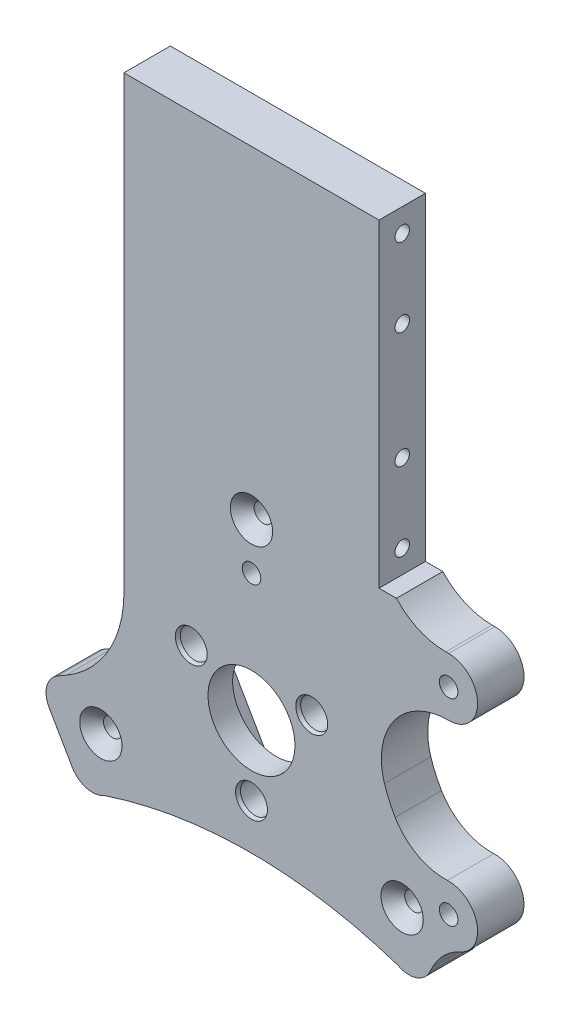
SolidWorks part; units mm, degrees
ref_plane "Front Plane" through (0, 0, 0) normal (0, 0, 1) x (1, 0, 0)
ref_plane "Top Plane" through (0, 0, 0) normal (0, 1, 0) x (1, 0, 0)
ref_plane "Right Plane" through (0, 0, 0) normal (1, 0, 0) x (0, 0, -1)
sketch "Sketch1" plane through (0, 0, 0) normal (0, 0, 1) x (1, 0, 0)
  line L0 (-1000, 0) -> (49000, 0) construction
  line L1 (0, -1000) -> (0, 49000) construction
  line L2 (0, 0) -> (-37.6779, -21.7533) construction
  line L3 (0, 0) -> (34.4865, -19.9108) construction
  line L4 (10, -8.7457) -> (10, 8.7457) construction
  line L5 (10.3863, 10.4956) -> (-10.3863, 10.4956)
  line L6 (-14.2847, 3.7444) -> (-3.9035, -14.2421)
  line L7 (3.9036, -14.242) -> (14.2846, 3.7447)
  line L8 (9.0941, -5.2486) -> (-10.3863, 5.9944) construction
  line L9 (0, -11.9891) -> (0, 10.4956) construction
  line L10 (10.3863, 5.9946) -> (-9.0941, -5.2488) construction
  line L11 (-30.909, -22.4641) -> (-34.909, -15.5359)
  line L12 (-32, -9.2376) -> (-33.4449, -10.0718)
  line L13 (-25, -23.6714) -> (-25.4449, -23.9282)
  line L14 (24.7944, -23.6821) -> (25.2453, -23.9282)
  line L15 (30.7512, -22.1827) -> (34.3345, -14.8973)
  line L16 (22, 49.7573) -> (-22, 49.7573)
  line L17 (22, 49.7573) -> (22, 38.5054)
  line L18 (32, -9.2376) -> (32.7451, -9.6678)
  line L19 (-22, 49.7573) -> (-22, 8.0829)
  line L20 (-4, 6.9282) -> (-41.6779, -14.8251) construction
  line L21 (34, 27.0109) -> (33.4945, 27.0109)
  line L22 (34, 17.0109) -> (33.8909, 17.0109)
  line L25 (-12, 0) -> (-12.0927, -0.0535)
  circle A0 centre (0, 0) radius 30 construction
  circle A1 centre (0, 0) radius 7.5
  circle A2 centre (0, 30) radius 4 construction
  circle A3 centre (25.9808, -15) radius 4 construction
  circle A4 centre (-25.9808, -15) radius 4 construction
  arc A5 (-10.3863, 10.4956) -> (-14.2847, 3.7444) centre (-10.3863, 5.9944) ccw
  arc A6 (-3.9035, -14.2421) -> (3.9036, -14.242) centre (0, -11.9891) ccw
  arc A7 (14.2846, 3.7447) -> (10.3863, 10.4956) centre (10.3863, 5.9946) ccw
  circle A8 centre (27.3746, 42.204) radius 2.5
  circle A9 centre (-27.6254, 42.204) radius 2.5
  arc A10 (32, -9.2376) -> (22.9322, 2.0481) centre (42, 8.0829) cw
  arc A11 (-22, 8.0829) -> (-32, -9.2376) centre (-42, 8.0829) cw
  arc A12 (25.2453, -23.9282) -> (-25.4449, -23.9282) centre (-0.0998, -99.8072) ccw
  arc A13 (30.7512, -22.1827) -> (25.2453, -23.9282) centre (27.1619, -20.4173) cw
  arc A14 (32.7451, -9.6678) -> (34.3345, -14.8973) centre (30.7451, -13.1319) cw
  arc A15 (-30.909, -22.4641) -> (-25.4449, -23.9282) centre (-27.4449, -20.4641) ccw
  arc A16 (-33.4449, -10.0718) -> (-34.909, -15.5359) centre (-31.4449, -13.5359) ccw
  circle A17 centre (34, -11.9891) radius 5
  arc A18 (34, 17.0109) -> (34, 27.0109) centre (34, 22.0109) ccw
  arc A19 (22, 38.5054) -> (33.4945, 27.0109) centre (33.4945, 38.5054) ccw
  arc A20 (33.8909, 17.0109) -> (22.9322, 2.0481) centre (33.8909, 5.5165) ccw
  point P4 (0, 0)
  point P19 (0, 0)
  point P21 (10, 0)
  point P40 (0, 0.9917)
  point P46 (0, 49.7573)
  point P47 (-32.909, -19)
  point P62 (28.909, -25.9282)
  point P67 (-28.909, -25.9282)
  line B0 (37, -11.9891) -> (-75, -11.9891) construction
  line B1 (0, -11.9891) -> (0, 22.0109) construction
  line B2 (-14.25, -36.1891) -> (-14.25, -11.9891) construction
  line B3 (-29.75, -13.311) -> (-29.75, -10.6672) construction
  line B4 (-39.75, -13.2558) -> (-39.75, -10.7223) construction
  line B5 (34, -11.9891) -> (34, 22.0109) construction
  line B6 (37, 27.0109) -> (37, -16.9891) construction
  line B7 (37, 27.0109) -> (-3, 27.0109) construction
  line B8 (37, -16.9891) -> (-3, -16.9891) construction
  line B9 (-14.25, -11.9891) -> (-14.25, 75.8256) construction
  line B10 (-3, 27.0109) -> (-3, -16.9891) construction
  dimension "D1" = 60
  dimension "D4" = 15
  dimension "D5" = 3
  dimension "D7" = 55
  dimension "D9" = 8
  dimension "D11" = 20
  dimension "D12" = 11.4945
  dimension "D13" = 4
  dimension "D14" = 4
  dimension "D15" = 11.4945
  dimension "D2" = 120
  dimension "D3" = 120
  dimension "D6" = 10
  dimension "D8" = 44
  dimension "D10" = 8
sketch_block_instance "HemeraFrontContraints-3"
sketch_block "HemeraFrontContraints" parameters "D1"=34, "D2"=48.25, "D3"=63.75, "D4"=73.75, "D5"=24.2, "D6"=34, "D7"=34, "D8"=31.699, "D9"=36.9763, "D10"=44
sketch "Sketch2" plane through (0, 0, 0) normal (0, 1, 0) x (1, 0, 0)
  line L0 (52, -10) -> (52, -104) construction
  line L1 (-49, 0) -> (49, 0) construction
  line L2 (-52, -10) -> (-52, -104) construction
  line L3 (-52, -104) -> (52, -104) construction
  line L4 (0, 0) -> (0, -30) construction
  line L7 (-52, -10) -> (-49, -10) construction
  line L8 (-49, 0) -> (-49, -10) construction
  line L11 (52, -10) -> (49, -10) construction
  line L12 (49, 0) -> (49, -10) construction
  point P12 (0, -104)
  dimension "D1" = 98
  dimension "D2" = 104
  dimension "D3" = 30
  dimension "D4" = 10
  dimension "D7" = 104
extrude "Boss-Extrude1" add sketch "Sketch1" along normal blind 8 contours A7 L7 A6 L6 A5 L5 | L17 | L19 | L16 L19 L17 | A10 A17 L15 A14 L18 | L15 A17 A10 L18 A14 region at (1.5486, 13.9173, 0) region at (31.8342, -12.7141, 0) region at (35.6729, -11.4291, 0)
extrude "Boss-Extrude2" add sketch "Sketch1<3>" along normal blind 4.25 from offset 3.75 contours L7 A7 L5 A5 L6 A6 A1 region at (13.936, 8.0445, 0)
sketch "Sketch1<3>" plane through (0, 0, 0) normal (0, 0, 1) x (1, 0, 0) same geometry as "Sketch1"
sketch "Sketch15" plane through (0, 49.7573, 0) normal (0, 1, 0) x (1, 0, 0)
  line L4 (22, 0) -> (-22, 0)
  line L5 (-22, 0) -> (-22, -8)
  line L6 (-22, -8) -> (22, -8)
  line L7 (22, -8) -> (22, 0)
  line L8 (22, 0) -> (-22, 0)
  line L9 (-22, 0) -> (-22, -8)
  line L10 (-22, -8) -> (22, -8)
  line L11 (22, -8) -> (22, 0)
  dimension "D1" = 0
extrude "Boss-Extrude3" add sketch "Sketch15" along normal blind 36
sketch "Sketch4" plane through (0, 0, 0) normal (0, 0, -1) x (-1, 0, 0)
  line L0 (0, 26) -> (0, 34)
  arc A0 (0, 26) -> (0, 34) centre (0, 30) ccw
revolve "Cut-Revolve1" cut sketch "Sketch4" angle 360 about L0
sketch "Sketch22" plane through (0, 0, 8) normal (0, 0, 1) x (1, 0, 0)
  line L0 (22, 49.7573) -> (22, 38.5054) construction
  line L1 (22, 40.7573) -> (27, 40.7573)
  line L2 (22, 40.7573) -> (22, 30.7573)
  line L3 (22, 30.7573) -> (27, 30.7573)
  line L4 (27, 40.7573) -> (27, 30.7573)
  dimension "D1" = 10
  dimension "D2" = 5
  dimension "D3" = 30.7573
extrude "Cut-Extrude1" cut sketch "Sketch22" against normal blind 10
sketch "Sketch5" plane through (0, 0, 0) normal (0, 0, -1) x (-1, 0, 0)
  line L0 (-22.5167, -13) -> (-29.4449, -17)
  line L1 (0, 0) -> (-34.4865, -19.9108) construction
  arc A0 (-22.5167, -13) -> (-29.4449, -17) centre (-25.9808, -15) ccw
revolve "Cut-Revolve2" cut sketch "Sketch5" angle 360 about L0
sketch "Sketch6" plane through (0, 0, 0) normal (0, 0, -1) x (-1, 0, 0)
  line L0 (22.5167, -13) -> (29.4449, -17)
  line L1 (0, 0) -> (37.6779, -21.7533) construction
  arc A0 (22.5167, -13) -> (29.4449, -17) centre (25.9808, -15) ccw
revolve "Cut-Revolve3" cut sketch "Sketch6" angle 360 about L0
hole_wizard "CSK for M3 Flat Head Machine Screw1" positions "Sketch7" profile "Sketch8" countersink size "M3" standard "ANSI Metric" end condition through all
sketch "Sketch7" plane through (0, 0, 8) normal (0, 0, 1) x (1, 0, 0)
  point P0 (0, 30)
  point P3 (25.9808, -15)
  point P6 (-25.9808, -15)
sketch "Sketch8" plane through (0, 30, 8) normal (1, 0, 0) x (0, -1, 0)
  line L0 (0, 0) -> (0, 8)
  line L1 (0, 8) -> (1.6, 8)
  line L2 (1.6, 8) -> (1.6, 2.05)
  line L3 (1.6, 2.05) -> (3.65, 0)
  line L5 (3.65, 0) -> (0, 0)
  line L6 (-1.6, 2.05) -> (-3.65, 0) construction
  line L11 (0, -6.35) -> (0, 107.95) construction
  dimension "Thru Hole Dia." = 3.2
  dimension "Thru Hole Depth" = 8
  dimension "Near C'Sink Dia." = 7.3
  dimension "Near C'Sink Angle" = 90
hole_wizard "CBORE for M3 SBHCS2" positions "Sketch11" profile "Sketch12" counterbore size "M3" standard "ANSI Metric" end condition through all
sketch "Sketch11" plane through (0, 0, 0) normal (0, 0, -1) x (-1, 0, 0)
  point P0 (-34, 22.0109)
  point P3 (0, 22.0109)
  point P6 (0, -11.9891)
  point P19 (-34, -11.9891)
sketch "Sketch12" plane through (34, 22.0109, 0) normal (1, 0, 0) x (0, 1, 0)
  line L0 (0, 0) -> (0, 8)
  line L1 (0, 8) -> (1.6, 8)
  line L3 (1.6, 8) -> (1.6, 3)
  line L4 (3.35, 3) -> (1.6, 3)
  line L5 (3.35, 3) -> (3.35, 0.025)
  line L6 (3.35, 0.025) -> (3.375, 0)
  line L7 (3.375, 0) -> (0, 0)
  line L8 (-3.35, 0.025) -> (-3.375, 0) construction
  line L11 (0, -6.35) -> (0, 107.95) construction
  dimension "Thru Hole Dia." = 3.2
  dimension "Thru Hole Depth" = 8
  dimension "C'Bore Dia." = 6.7
  dimension "C'Bore Depth" = 3
  dimension "Near C'Sink Dia." = 6.75
  dimension "Near C'Sink Angle" = 90
hole_wizard "CSK for M4 Flat Head Machine Screw1" positions "Sketch13" profile "Sketch14" countersink size "M4" standard "ANSI Metric" end condition through all
sketch "Sketch13" plane through (0, 0, 8) normal (0, 0, 1) x (1, 0, 0)
  point P0 (-10.3863, 5.9944)
  point P3 (10.3863, 5.9946)
  point P6 (0, -11.9891)
sketch "Sketch14" plane through (-10.3863, 5.9944, 8) normal (1, 0, 0) x (0, -1, 0)
  line L0 (0, 0) -> (0, 8)
  line L1 (0, 8) -> (2.5, 8)
  line L2 (2.5, 8) -> (2.5, 0.6036)
  line L3 (2.5, 0.6036) -> (2.75, 0)
  line L5 (2.75, 0) -> (0, 0)
  line L6 (-2.5, 0.6036) -> (-2.75, 0) construction
  line L11 (0, -6.35) -> (0, 107.95) construction
  dimension "Thru Hole Dia." = 5
  dimension "Thru Hole Depth" = 8
  dimension "Near C'Sink Dia." = 5.5
  dimension "Near C'Sink Angle" = 45
fillet "Fillet1" radius 10 2 edges at (30.5834, -8.3385, 4) (33.328, -16.9437, 4)
hole_wizard "Tap Drill for M3x0.5 Tap4" positions "Sketch25" profile "Sketch26" hole size "M3x0.5" standard "ANSI Metric"
sketch "Sketch25" plane through (22, 0, 0) normal (1, 0, 0) x (0, 0, -1)
  line L0 (-8, 85.7573) -> (0, 85.7573) construction
  line L1 (0, 85.7573) -> (0, 30.7573) construction
  point P0 (-4, 81.7573)
  point P2 (-4, 68.2573)
  point P4 (-4, 34.7573)
  point P6 (-4, 48.2573)
  dimension "D1" = 4
  dimension "D2" = 13.5
  dimension "D3" = 13.5
  dimension "D4" = 20
  dimension "D5" = 4
sketch "Sketch26" plane through (22, 81.7573, 4) normal (0, 1, 0) x (0, 0, -1)
  line L0 (0, 0) -> (0, 5.7511)
  line L1 (0, 5.7511) -> (1.25, 5)
  line L2 (1.25, 5) -> (1.25, 0)
  line L5 (1.25, 0) -> (0, 0)
  line L10 (0, 5.7511) -> (-1.25, 5) construction
  line L11 (0, -6.35) -> (0, 107.95) construction
  dimension "Hole Dia." = 2.5
  dimension "Hole Depth" = 5
  dimension "Drill Angle" = 118
mirror "Mirror1" about plane through (0, 0, 0) normal (1, 0, 0) of "Tap Drill for M3x0.5 Tap4"
sketch "Sketch27" plane through (0, 0, 0) normal (0, 0, -1) x (-1, 0, 0)
  line L0 (-22, 70.5898) -> (22, 70.5898) construction
  line L1 (-22, 85.7573) -> (-22, 30.7573) construction
  line L2 (22, 85.7573) -> (22, 8.0829) construction
  text T0 "HEMERA" font "Century Gothic" height 7.5
extrude "Cut-Extrude2" cut sketch "Sketch27" against normal blind 1
sketch "Sketch28" plane through (0, 0, 8) normal (0, 0, 1) x (1, 0, 0)
  line L1 (-17.5116, 114.5438) -> (10.9884, 114.5438) construction
  line L2 (-17.5116, 114.5438) -> (-17.5116, 51.0438) construction
  line L3 (-17.5116, 51.0438) -> (10.9884, 51.0438) construction
  line L4 (10.9884, 114.5438) -> (10.9884, 51.0438) construction
  dimension "D1" = 63.5
  dimension "D2" = 28.5
